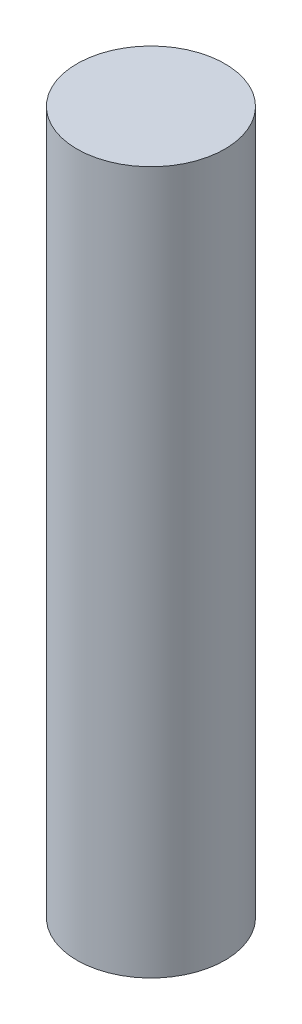
SolidWorks part; units mm, degrees
ref_plane "Alzado" through (0, 0, 0) normal (0, 0, 1) x (1, 0, 0)
ref_plane "Planta" through (0, 0, 0) normal (0, 1, 0) x (1, 0, 0)
ref_plane "Vista lateral" through (0, 0, 0) normal (1, 0, 0) x (0, 0, -1)
sketch "Croquis1" plane through (0, 0, 0) normal (0, 1, 0) x (1, 0, 0)
  circle A0 centre (0, 0) radius 4
  dimension "D1" = 8
extrude "Saliente-Extruir1" add sketch "Croquis1" along normal blind 38
